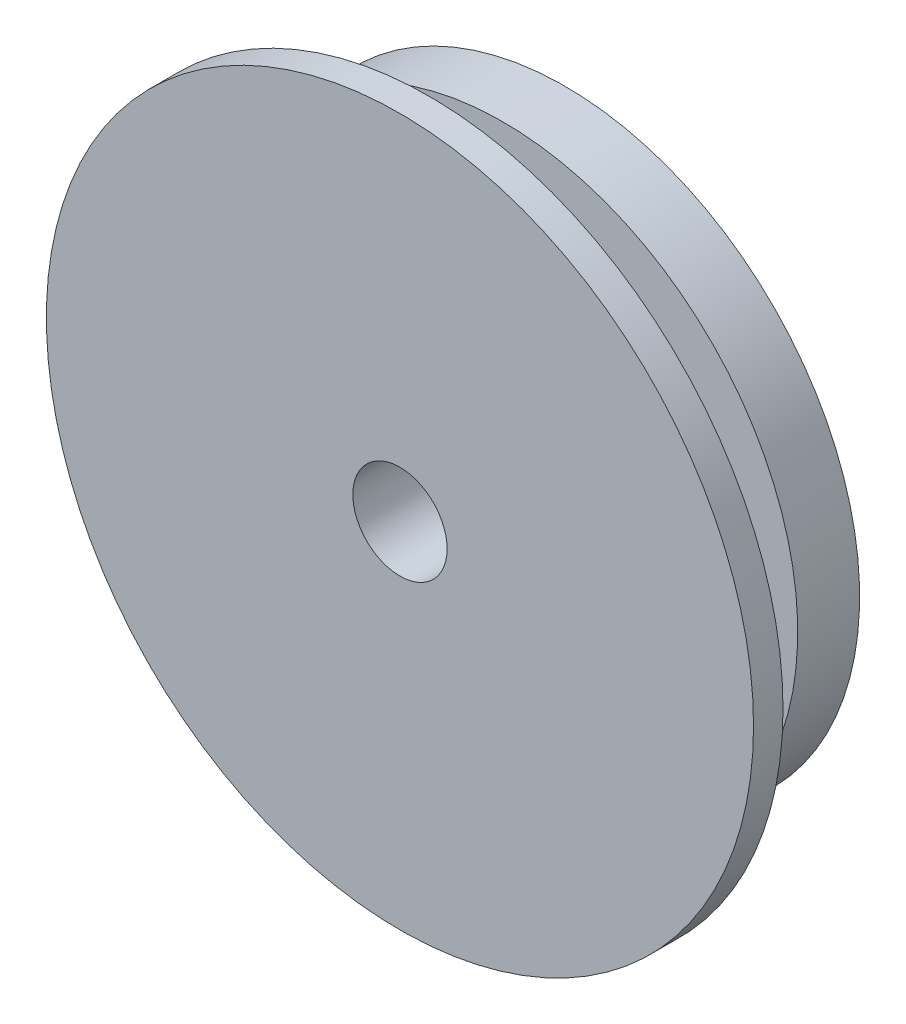
SolidWorks part; units mm, degrees
material "Resina de melamina"
ref_plane "Alzado" through (0, 0, 0) normal (0, 0, 1) x (1, 0, 0)
ref_plane "Planta" through (0, 0, 0) normal (0, 1, 0) x (1, 0, 0)
ref_plane "Vista lateral" through (0, 0, 0) normal (1, 0, 0) x (0, 0, -1)
sketch "Croquis1" plane through (0, 0, 0) normal (0, 0, 1) x (1, 0, 0)
  circle A0 centre (0, 0) radius 11
  circle A1 centre (0, 0) radius 25
  dimension "D1" = 50
  dimension "D2" = 22
extrude "Saliente-Extruir1" add sketch "Croquis1" along normal blind 15.5
ref_plane "Plano1" through (0, 0, 6) normal (0, 0, -1) x (-1, 0, 0)
sketch "Croquis3" plane through (0, 0, 6) normal (0, 0, -1) x (-1, 0, 0)
  circle A0 centre (0, 0) radius 11
  circle A1 centre (0, 0) radius 9.5
  dimension "D1" = 19
extrude "Saliente-Extruir2" add sketch "Croquis3" against normal through all
sketch "Croquis4" plane through (0, 0, 15.5) normal (0, 0, 1) x (1, 0, 0)
  circle A0 centre (0, 0) radius 11
  circle A1 centre (0, 0) radius 4
  dimension "D1" = 8
extrude "Saliente-Extruir3" add sketch "Croquis4" against normal blind 2
sketch "Croquis5" plane through (0, 0, 15.5) normal (0, 0, 1) x (1, 0, 0)
  circle A0 centre (0, 0) radius 25
  circle A1 centre (0, 0) radius 30
  dimension "D1" = 60
extrude "Saliente-Extruir4" add sketch "Croquis5" against normal blind 2.5
ref_plane "Plano2" through (0, 0, 10.75) normal (0, 0, -1) x (-1, 0, 0)
sketch "Croquis6" plane through (0, 0, 10.75) normal (0, 0, -1) x (-1, 0, 0)
  circle A1 centre (0, 0) radius 25
  circle A2 centre (0, 0) radius 19
  dimension "D1" = 38
extrude "Cortar-Extruir1" cut sketch "Croquis6" along normal blind 4
sketch "Croquis7" plane through (0, 0, 0) normal (0, 0, -1) x (-1, 0, 0)
  circle A0 centre (0, 0) radius 11
  circle A1 centre (0, 0) radius 4
extrude "Saliente-Extruir5" add sketch "Croquis7" against normal through all
sketch "Croquis8" plane through (0, 0, 0) normal (0, 0, -1) x (-1, 0, 0)
  circle A0 centre (0, 0) radius 6.1
  circle A1 centre (0, 0) radius 4
  dimension "D1" = 12.2
extrude "Saliente-Extruir6" add sketch "Croquis8" along normal blind 2
sketch "Croquis11" plane through (0, 0, 0) normal (0, 0, -1) x (-1, 0, 0)
  circle A0 centre (0, 0) radius 15
  circle A1 centre (0, 0) radius 25
  dimension "D1" = 30
extrude "Cortar-Extruir2" cut sketch "Croquis11" against normal blind 1.5
